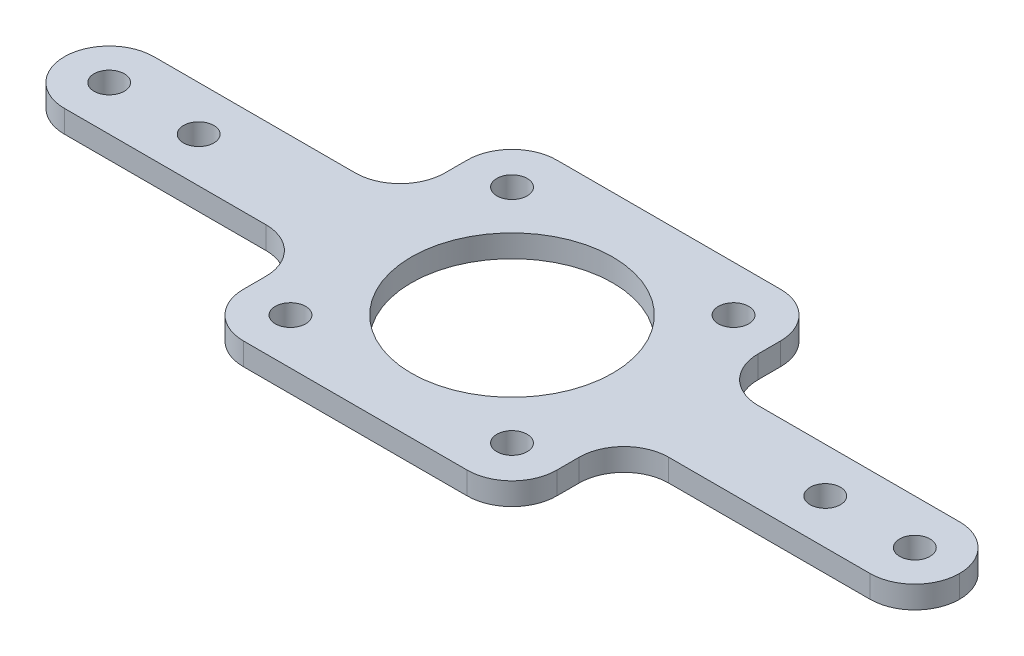
SolidWorks part; units mm, degrees
material "6061-T6 (SS)"
ref_plane "Front Plane" through (0, 0, 0) normal (0, 0, 1) x (1, 0, 0)
ref_plane "Top Plane" through (0, 0, 0) normal (0, 1, 0) x (1, 0, 0)
ref_plane "Right Plane" through (0, 0, 0) normal (1, 0, 0) x (0, 0, -1)
sketch "Sketch1" plane through (0, 0, 0) normal (0, 1, 0) x (1, 0, 0)
  line L1 (-22.225, -22.225) -> (22.225, -22.225)
  line L2 (-22.225, -22.225) -> (-22.225, 22.225)
  line L3 (-22.225, 22.225) -> (22.225, 22.225)
  line L4 (22.225, -22.225) -> (22.225, 22.225)
  line L5 (-22.225, -22.225) -> (22.225, 22.225) construction
  line L6 (-22.225, 22.225) -> (22.225, -22.225) construction
  line L7 (63.5, -6.35) -> (-63.5, -6.35)
  line L8 (63.5, -6.35) -> (63.5, 6.35)
  line L9 (63.5, 6.35) -> (-63.5, 6.35)
  line L10 (-63.5, -6.35) -> (-63.5, 6.35)
  line L11 (63.5, -6.35) -> (-63.5, 6.35) construction
  line L12 (63.5, 6.35) -> (-63.5, -6.35) construction
  point P0 (0, 0)
  point P6 (0, 0)
  dimension "D1" = 44.45
  dimension "D2" = 127
  dimension "D3" = 12.7
  dimension "D4" = 44.45
extrude "Boss-Extrude1" add sketch "Sketch1" along normal blind 3.175 contours L4 L9 L2 L7 | L4 L7 L2 L1 | L8 L9 L4 L7 | L9 L4 L3 L2 | L10 L7 L2 L9 region at (0, 0, 14.2875) region at (-42.8625, 0, 0) region at (0, 0, 0) region at (42.8625, 0, 0) region at (0, 0, -14.2875)
sketch "Sketch3" plane through (0, 3.175, 0) normal (0, 1, 0) x (1, 0, 0)
  circle A0 centre (0, 0) radius 14.2875
  dimension "D1" = 28.575
extrude "Cut-Extrude1" cut sketch "Sketch3" against normal through all
hole_wizard "#18 (0.1695) Diameter Hole1" positions "Sketch4" profile "Sketch5" hole size "#18" standard "ANSI Inch" end condition through all
sketch "Sketch4" plane through (0, 3.175, 0) normal (0, 1, 0) x (1, 0, 0)
  line L0 (0, 0) -> (0, -22.225) construction
  line L2 (0, 0) -> (-15.7154, -15.7154) construction
  circle A0 centre (0, 0) radius 22.225 construction
  point P6 (-15.7154, -15.7154)
  dimension "D2" = 44.45
  dimension "D1" = 45
sketch "Sketch5" plane through (-15.7154, 3.175, 15.7154) normal (1, 0, 0) x (0, 0, 1)
  line L0 (0, 0) -> (0, 3.175)
  line L1 (0, 3.175) -> (2.1526, 3.175)
  line L2 (2.1526, 3.175) -> (2.1526, 0)
  line L5 (2.1526, 0) -> (0, 0)
  line L11 (0, -6.35) -> (0, 107.95) construction
  dimension "Thru Hole Dia." = 4.3053
  dimension "Thru Hole Depth" = 3.175
pattern_circular "CirPattern1" count 4 over 360 about axis through (0, 0, 0) along (0, 1, 0) of "#18 (0.1695) Diameter Hole1"
fillet "Fillet1" radius 6.35 4 edges at (22.225, 1.5875, -6.35) (22.225, 1.5875, 6.35) (-22.225, 1.5875, 6.35) (-22.225, 1.5875, -6.35)
fillet "Fillet2" radius 6.35 8 edges at (-63.5, 1.5875, 6.35) (-63.5, 1.5875, -6.35) (-22.225, 1.5875, -22.225) (22.225, 1.5875, -22.225) (63.5, 1.5875, -6.35) (63.5, 1.5875, 6.35) (22.225, 1.5875, 22.225) (-22.225, 1.5875, 22.225)
hole_wizard "#18 (0.1695) Diameter Hole2" positions "Sketch6" profile "Sketch7" hole size "#18" standard "ANSI Inch" end condition through all
sketch "Sketch6" plane through (0, 3.175, 0) normal (0, 1, 0) x (1, 0, 0)
  line L0 (0, 0) -> (57.15, 0) construction
  point P0 (44.45, 0)
  point P2 (57.15, 0)
  dimension "D1" = 12.7
  dimension "D2" = 44.45
sketch "Sketch7" plane through (44.45, 3.175, 0) normal (1, 0, 0) x (0, 0, 1)
  line L0 (0, 0) -> (0, 3.175)
  line L1 (0, 3.175) -> (2.1526, 3.175)
  line L2 (2.1526, 3.175) -> (2.1526, 0)
  line L5 (2.1526, 0) -> (0, 0)
  line L11 (0, -6.35) -> (0, 107.95) construction
  dimension "Thru Hole Dia." = 4.3053
  dimension "Thru Hole Depth" = 3.175
mirror "Mirror1" about plane through (0, 0, 0) normal (1, 0, 0) of "#18 (0.1695) Diameter Hole2"
